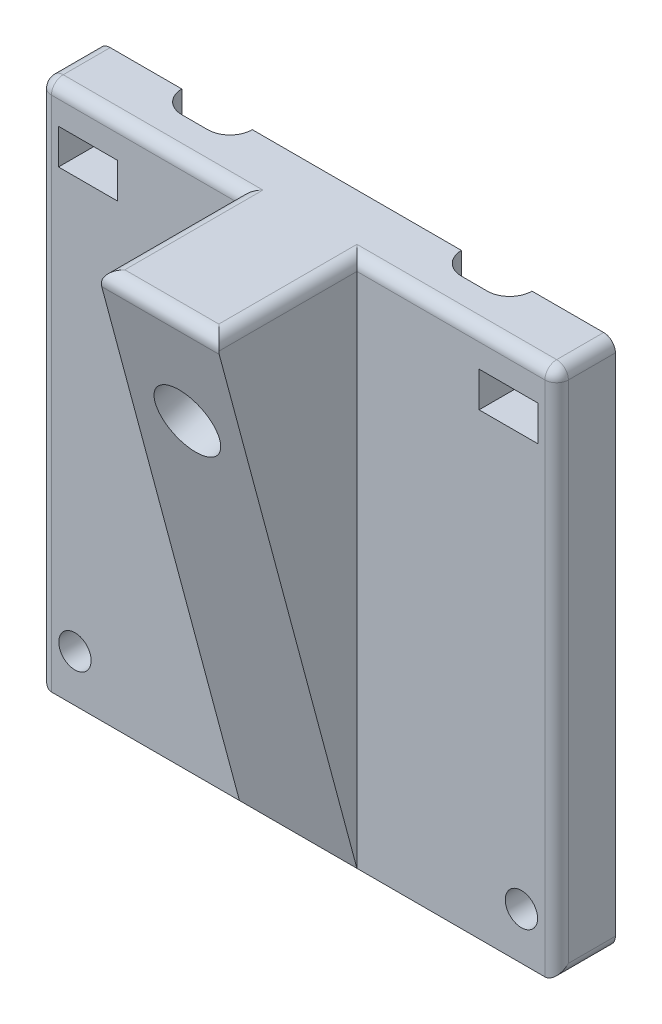
SolidWorks part; units mm, degrees
ref_plane "Front Plane" through (0, 0, 0) normal (0, 0, 1) x (1, 0, 0)
ref_plane "Top Plane" through (0, 0, 0) normal (0, 1, 0) x (1, 0, 0)
ref_plane "Right Plane" through (0, 0, 0) normal (1, 0, 0) x (0, 0, -1)
sketch "Sketch1" plane through (0, 0, 0) normal (0, 0, 1) x (1, 0, 0)
  line L1 (-22, 22.5) -> (22, 22.5)
  line L2 (-22, 22.5) -> (-22, -22.5)
  line L3 (-22, -22.5) -> (22, -22.5)
  line L4 (22, 22.5) -> (22, -22.5)
  line L5 (-22, 22.5) -> (22, -22.5) construction
  line L6 (-22, -22.5) -> (22, 22.5) construction
  point P0 (0, 0)
  dimension "D1" = 44
  dimension "D2" = 45
extrude "Base" add sketch "Sketch1" along normal blind 5
sketch "Sketch2" plane through (0, 22.5, 0) normal (0, 1, 0) x (1, 0, 0)
  line L0 (22, 0) -> (-22, 0) construction
  line L1 (-14.9, 0) -> (-8.9, 0)
  line L2 (0, 0) -> (0, -5) construction
  line L3 (22, -5) -> (-22, -5) construction
  line L5 (-14.9, 0) -> (-14.9, -5) construction
  line L6 (-13, -1.9) -> (-10.8, -1.9)
  line L7 (13, -1.9) -> (10.8, -1.9)
  line L8 (14.9, 0) -> (8.9, 0)
  arc A2 (-14.9, 0) -> (-13, -1.9) centre (-13, 0) ccw
  arc A3 (-10.8, -1.9) -> (-8.9, 0) centre (-10.8, 0) ccw
  arc A4 (14.9, 0) -> (13, -1.9) centre (13, 0) cw
  arc A5 (10.8, -1.9) -> (8.9, 0) centre (10.8, 0) cw
  point P0 (-11.9, 0)
  dimension "D1" = 11.9
  dimension "D2" = 6
  dimension "D3" = 1.9
extrude "Wire Grooves" cut sketch "Sketch2" against normal through all
sketch "Sketch4" plane through (22, 0, 0) normal (1, 0, 0) x (0, 0, -1)
  line L0 (-5, -22.5) -> (-5, 22.5)
  line L1 (-5, -22.5) -> (-17.0577, 22.5)
  line L2 (-17.0577, 22.5) -> (-5, 22.5)
  dimension "D1" = 15
extrude "Slanted Screw Platform" add sketch "Sketch4" against normal mid plane 10 from surface starting at plane "Right Plane"
sketch "Sketch5" plane through (0, -2.7572, 10.2901) normal (0, -0.2588, 0.9659) x (1, 0, 0)
  line L0 (0, 0) -> (0, 26.1482) construction
  line L1 (-5, 26.1482) -> (5, 26.1482) construction
  circle A0 centre (0, 16) radius 2.75
  dimension "D1" = 5.5
  dimension "D2" = 16
extrude "Mounting Hole Screw Insertion" cut sketch "Sketch5" against normal through all
sketch "Sketch6" plane through (0, 0, 5) normal (0, 0, 1) x (1, 0, 0)
  line L0 (0, 22.5) -> (0, -22.5) construction
  line L1 (-5, 22.5) -> (5, 22.5) construction
  line L2 (-5, -22.5) -> (5, -22.5) construction
  line L3 (-22, 22.5) -> (-22, -22.5) construction
  line L4 (-20.4, 19.5) -> (-15.4, 19.5)
  line L5 (-20.4, 19.5) -> (-20.4, 16.5)
  line L6 (-20.4, 16.5) -> (-15.4, 16.5)
  line L7 (-15.4, 19.5) -> (-15.4, 16.5)
  line L8 (20.4, 16.5) -> (15.4, 16.5)
  line L9 (15.4, 19.5) -> (15.4, 16.5)
  line L10 (20.4, 19.5) -> (15.4, 19.5)
  line L11 (20.4, 19.5) -> (20.4, 16.5)
  line L12 (-5, 22.5) -> (-22, 22.5) construction
  point P10 (-17.9, 19.5)
  dimension "D1" = 5
  dimension "D2" = 3
  dimension "D3" = 3
  dimension "D4" = 4.1
extrude "Zip Tie Slots" cut sketch "Sketch6" against normal through all
sketch "Sketch7" plane through (0, 0, 5) normal (0, 0, 1) x (1, 0, 0)
  line L0 (-22, 22.5) -> (-22, -22.5) construction
  line L1 (-22, -22.5) -> (-5, -22.5) construction
  line L2 (0, 22.5) -> (0, -22.5) construction
  line L3 (-5, 22.5) -> (5, 22.5) construction
  line L4 (-5, -22.5) -> (5, -22.5) construction
  circle A0 centre (-19, -18.5) radius 1.375
  circle A1 centre (19, -18.5) radius 1.375
  dimension "D1" = 2.75
  dimension "D2" = 3
  dimension "D3" = 4
extrude "Mount Clamping Holes" cut sketch "Sketch7" against normal through all
fillet "Edge Fillets" radius 1 11 edges at (22, 0, 5) (-5, 22.5, 11.0289) (0, 22.5, 17.0577) (5, 22.5, 11.0289) (13.5, 22.5, 5) (-22, 0, 5) (-13.5, 22.5, 5) (22, -22.5, 2.5) (-22, -22.5, 2.5) (22, 22.5, 2.5) (-22, 22.5, 2.5)
